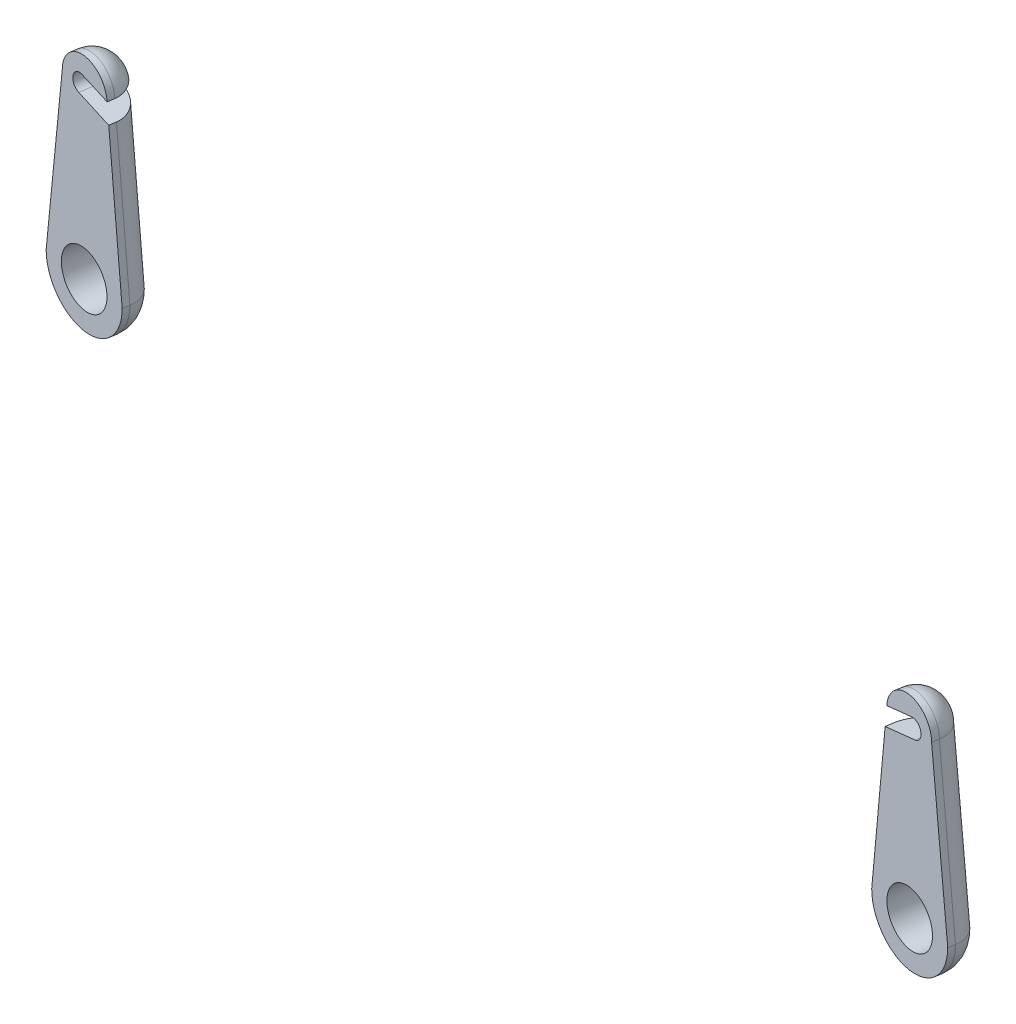
SolidWorks part; units mm, degrees
ref_plane "Front Plane" through (0, 0, 0) normal (0, 0, 1) x (1, 0, 0)
ref_plane "Top Plane" through (0, 0, 0) normal (0, 1, 0) x (1, 0, 0)
ref_plane "Right Plane" through (0, 0, 0) normal (1, 0, 0) x (0, 0, -1)
sketch "Sketch1" plane through (8.1146, -3.2834, -55.6766) normal (0.1442, 0, -0.9895) x (-0.9895, 0, -0.1442)
  line L0 (7.7839, 205.4844) -> (7.7839, 234.9484) construction
  line L1 (13.4843, 234.9484) -> (1.3539, 234.9484) construction
  line L2 (7.9153, 238.4844) -> (-3.6461, 238.4844) construction
  line L3 (-1.1061, 205.4844) -> (2.6653, 238.4844)
  line L4 (13.1653, 238.4844) -> (16.6739, 205.4844)
  line L6 (-3.6461, 244.4784) -> (-3.6461, 234.9484) construction
  line L8 (7.7839, 234.9484) -> (7.7839, 205.4844) construction
  line L9 (7.7839, 205.4844) -> (-3.6461, 205.4844) construction
  line L12 (7.7839, 205.4844) -> (7.7839, 234.9484) construction
  arc A1 (13.1653, 238.4844) -> (2.6653, 238.4844) centre (7.9153, 238.4844) ccw
  arc A2 (-1.1061, 205.4844) -> (16.6739, 205.4844) centre (7.7839, 205.4844) ccw
  dimension "D3" = 10.5
  dimension "D5" = 8.89
  dimension "D1" = 29.464
  dimension "D2" = 29.464
  dimension "D4" = 33
  dimension "D7" = 29.464
  dimension "D8" = 11.43
extrude "Base Extrude" add sketch "Sketch1" along normal blind 6.35
sketch "Sketch3" plane through (9.0304, -3.2834, -61.9602) normal (0.1442, 0, -0.9895) x (-0.9895, 0, -0.1442)
  line L0 (14.7164, 236.6382) -> (6.9306, 238.4771) construction
  line L1 (14.3026, 234.8864) -> (6.5168, 236.7253)
  line L2 (15.1301, 238.39) -> (7.3444, 240.2289)
  line L3 (6.8573, 236.9701) -> (6.8573, 237.9784) construction
  arc A0 (14.3026, 234.8864) -> (15.1301, 238.39) centre (14.7164, 236.6382) ccw
  arc A1 (7.3444, 240.2289) -> (6.5168, 236.7253) centre (6.9306, 238.4771) ccw
  circle A2 centre (6.8573, 238.4941) radius 1.524 construction
  point P3 (10.8235, 237.5577)
  dimension "D1" = 1.8
  dimension "D2" = 8
ref_plane "Rear Mirror Plane " through (-103.2134, 0, -15.0429) normal (0.9895, 0, 0.1442) x (0.1442, 0, -0.9895)
fillet "Fillet1" radius 5 4 edges at (1.1978, 240.451, -63.1018) (1.3279, 193.311, -63.0828) (-5.7332, 218.701, -64.112) (8.259, 218.701, -62.0727)
extrude "Cut-Extrude1" cut sketch "Sketch3" against normal up to surface (6.35 mm away) up to face at (0.3471, 217.791, -56.8087)
mirror "Mirror2" about plane through (-103.2134, 0, -15.0429) normal (0.9895, 0, 0.1442) of bodies 109
sketch "Sketch4" plane through (9.0304, 0, -61.9602) normal (0.1442, 0, -0.9895) x (-0.9895, 0, -0.1442)
  line L0 (2.7459, 202.201) -> (7.7839, 202.201) construction
  circle A0 centre (7.7839, 202.201) radius 5.0381 construction
  circle A1 centre (7.7839, 202.201) radius 5.334
  dimension "D1" = 10.668
extrude "Cut-Extrude2" cut sketch "Sketch4" against normal up to surface (6.35 mm away) up to face at (0.0791, 224.8477, -56.8478)
mirror "Mirror3" about plane through (-103.2134, 0, -15.0429) normal (0.9895, 0, 0.1442) of "Cut-Extrude2"
